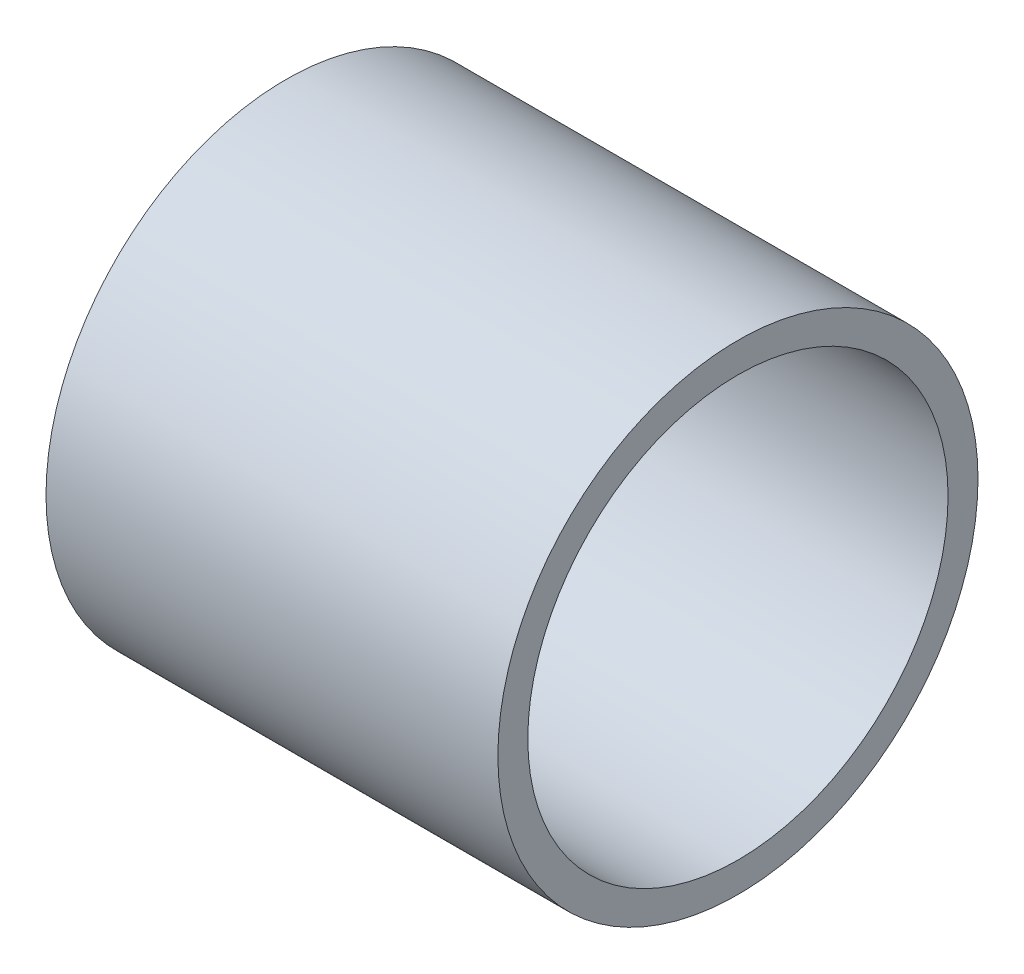
SolidWorks part; units mm, degrees
ref_plane "Front Plane" through (0, 0, 0) normal (0, 0, 1) x (1, 0, 0)
ref_plane "Top Plane" through (0, 0, 0) normal (0, 1, 0) x (1, 0, 0)
ref_plane "Right Plane" through (0, 0, 0) normal (1, 0, 0) x (0, 0, -1)
sketch "Sketch2" plane through (0, 0, 0) normal (0, 0, 1) x (1, 0, 0)
  line L0 (0, 0) -> (74.8146, 0) construction
  line L2 (0, 141.732) -> (304.8, 141.732)
  line L3 (0, 141.732) -> (0, 161.925)
  line L4 (0, 161.925) -> (304.8, 161.925)
  line L5 (304.8, 141.732) -> (304.8, 161.925)
  dimension "D1" = 141.732
  dimension "D3" = 304.8
  dimension "D2" = 161.925
revolve "Revolve1" add sketch "Sketch2" angle 360 about L0
equation "\"ID\"= 11.160in"
equation "\"OD\"= 12.75in"
equation "\"Length\"= 12in"
equation "\"D1@Sketch2\"=\"ID\"/2"
equation "\"D3@Sketch2\"=\"Length\""
equation "\"D2@Sketch2\"=\"OD\"/2"
